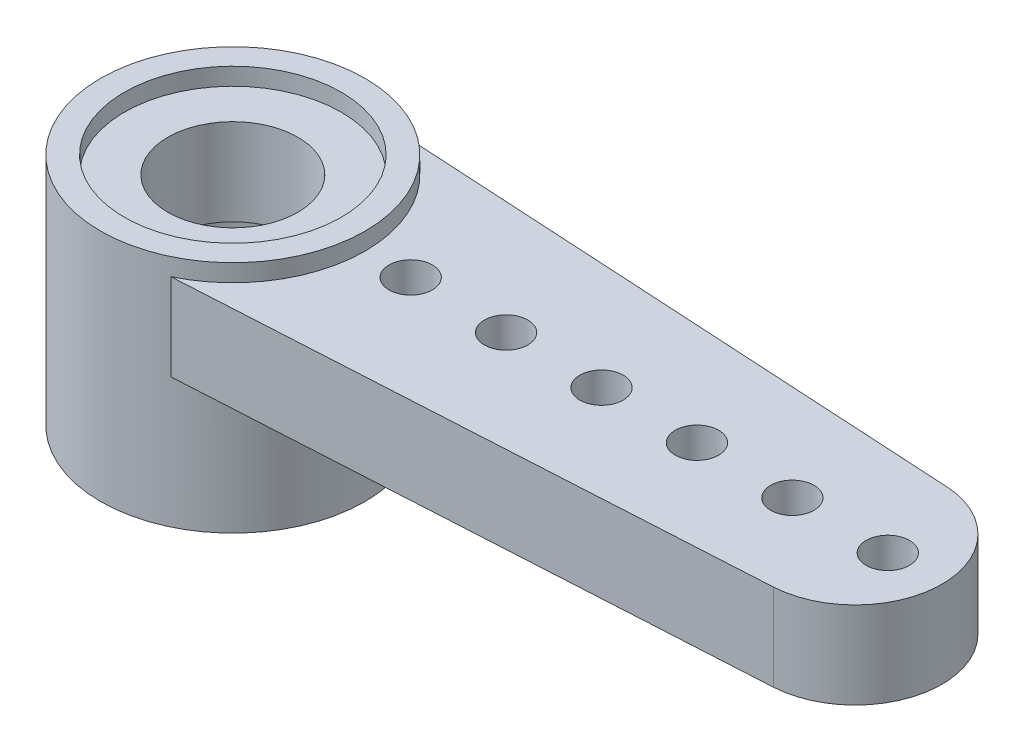
SolidWorks part; units mm, degrees
material "ABS"
ref_plane "Front Plane" through (0, 0, 0) normal (0, 0, 1) x (1, 0, 0)
ref_plane "Top Plane" through (0, 0, 0) normal (0, 1, 0) x (1, 0, 0)
ref_plane "Right Plane" through (0, 0, 0) normal (1, 0, 0) x (0, 0, -1)
sketch "Sketch1" plane through (0, 0, 0) normal (0, 1, 0) x (1, 0, 0)
  circle A0 centre (0, 0) radius 3.05
  circle A1 centre (0, 0) radius 2.5
  dimension "D1" = 6.1
  dimension "D2" = 5
extrude "Boss-Extrude1" add sketch "Sketch1" along normal blind 5.4
ref_plane "Plane1" through (0, 3, 0) normal (0, 1, 0) x (1, 0, 0)
sketch "Sketch2" plane through (0, 3, 0) normal (0, 1, 0) x (1, 0, 0)
  line L0 (1.3191, 2.75) -> (14.4609, 2)
  line L1 (14.4609, -2) -> (1.3191, -2.75)
  line L2 (-3.05, 2.0612) -> (-3.05, -1.8709) construction
  line L3 (16.35, 3.5453) -> (16.35, -6.4951) construction
  circle A0 centre (0, 0) radius 3.05 construction
  arc A1 (14.4609, 2) -> (14.4609, -2) centre (14.3467, 0) cw
  arc A2 (1.3191, 2.75) -> (1.3191, -2.75) centre (0, 0) ccw
  dimension "D1" = 19.4
  dimension "D2" = 5.5
  dimension "D3" = 4
extrude "Boss-Extrude2" add sketch "Sketch2" along normal blind 2
sketch "Sketch3" plane through (0, 5, 0) normal (0, 1, 0) x (1, 0, 0)
  line L0 (4.1, 0) -> (15.1, 0) construction
  circle A0 centre (4.1, 0) radius 0.5
  circle A1 centre (6.3, 0) radius 0.5
  circle A2 centre (8.5, 0) radius 0.5
  circle A3 centre (10.7, 0) radius 0.5
  circle A4 centre (12.9, 0) radius 0.5
  circle A5 centre (15.1, 0) radius 0.5
  dimension "D1" = 1
  dimension "D3" = 4.1
  dimension "D4" = 11
  dimension "D2" = 6
extrude "Cut-Extrude1" cut sketch "Sketch3" against normal up to next
sketch "Sketch6" plane through (0, 5, 0) normal (0, 1, 0) x (1, 0, 0)
  circle A0 centre (0, 0) radius 1.5
  dimension "D1" = 3
extrude "Cut-Extrude3" cut sketch "Sketch6" against normal up to next
